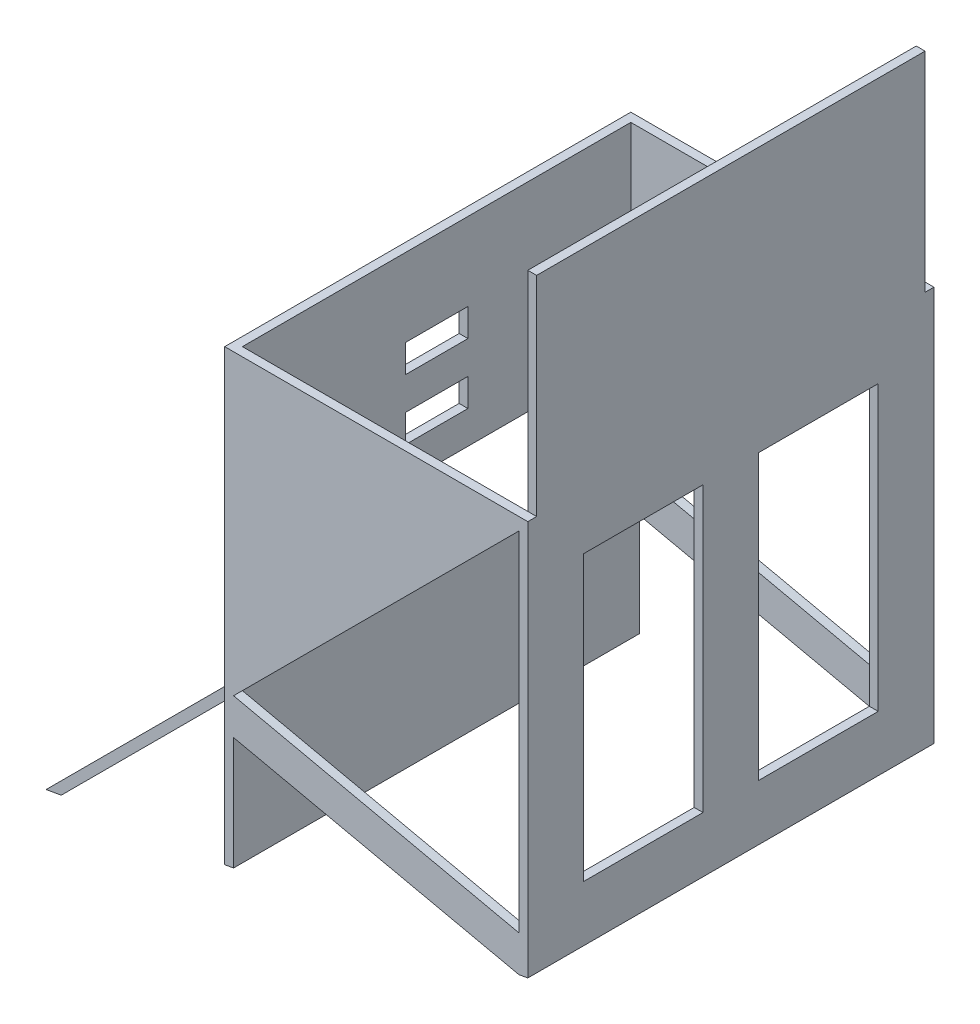
SolidWorks part; units mm, degrees
material "Teak"
ref_plane "Front Plane" through (0, 0, 0) normal (0, 0, 1) x (1, 0, 0)
ref_plane "Top Plane" through (0, 0, 0) normal (0, 1, 0) x (1, 0, 0)
ref_plane "Right Plane" through (0, 0, 0) normal (1, 0, 0) x (0, 0, -1)
sketch "Sketch1" plane through (0, 0, 0) normal (0, 1, 0) x (1, 0, 0)
  line L1 (-102.5, 139.5) -> (102.5, 139.5)
  line L2 (-102.5, 139.5) -> (-102.5, -139.5)
  line L3 (-102.5, -139.5) -> (102.5, -139.5)
  line L4 (102.5, 139.5) -> (102.5, -139.5)
  line L5 (-102.5, 139.5) -> (102.5, -139.5) construction
  line L6 (-102.5, -139.5) -> (102.5, 139.5) construction
  line L7 (-108.85, 145.85) -> (108.85, 145.85)
  line L8 (-108.85, 145.85) -> (-108.85, -145.85)
  line L9 (-108.85, -145.85) -> (108.85, -145.85)
  line L10 (108.85, 145.85) -> (108.85, -145.85)
  line L11 (-108.85, 145.85) -> (108.85, -145.85) construction
  line L12 (-108.85, -145.85) -> (108.85, 145.85) construction
  point P0 (0, 0)
  point P5 (0, 0)
  dimension "D1" = 279
  dimension "D2" = 205
  dimension "D3" = 6.35
  dimension "D4" = 6.35
sketch3d "3DSketch1"
  line L0 (102.5, 150, 0) -> (102.5, 0, 0) construction
  line L1 (102.5, 0, 0) -> (0, 0, 0) construction
  line L2 (102.5, 0, 102.7399) -> (102.5, 0, -102.7399) construction
  line L3 (102.5, 0, 0) -> (102.5, -285, 0) construction
  line L4 (102.5, -285, -65.8407) -> (102.5, -285, 65.8407) construction
  line L5 (102.5, 0, -139.5) -> (102.5, 0, 139.5) construction
  dimension "D1" = 150
  dimension "D2" = 285
ref_plane "Base Plane" through (51.25, -51.25, 0) normal (-0.7071, 0.7071, 0) x (0, 0, -1)
ref_plane "Launch Plane" through (51.8286, -293.9347, 0) normal (-0.1736, 0.9848, 0) x (0, 0, 1)
ref_plane "Box Bottom Plane (Approx)" through (0, -500, 0) normal (0, 1, 0) x (1, 0, 0)
extrude "Boss-Extrude1" add sketch "Sketch1" against normal up to surface (285 mm away) up to plane "Launch Plane"
sketch "Sketch7" plane through (0, 0, 0) normal (0, 0, 1) x (1, 0, 0)
  line L0 (102.5, 0) -> (-243.5111, -346.0111)
  line L1 (-243.5111, -346.0111) -> (-232.6084, -344.0887)
  line L2 (131.1629, 28.6629) -> (-28.6629, -131.1629) construction
  line L3 (119.735, 0) -> (-119.735, 0) construction
  line L4 (102.5, 0) -> (102.5, -8.9803)
  line L5 (102.5, -8.9803) -> (-232.6084, -344.0887)
  line L6 (123.1531, -281.3583) -> (-19.4958, -306.5112) construction
  dimension "D1" = 6.35
extrude "Boss-Extrude4" add sketch "Sketch7" against normal up to surface and the other way up to surface up to face at (0, -151.5368, -139.5) other way up to face at (0, -151.5368, 139.5)
sketch "Sketch8" plane through (0, 0, 0) normal (0, 1, 0) x (1, 0, 0)
  line L0 (108.85, 145.85) -> (108.85, -145.85) construction
  line L1 (102.5, 139.5) -> (108.85, 139.5)
  line L2 (102.5, 139.5) -> (102.5, -139.5)
  line L3 (102.5, -139.5) -> (108.85, -139.5)
  line L4 (108.85, 139.5) -> (108.85, -139.5)
  line L5 (-102.5, -139.5) -> (102.5, -139.5) construction
extrude "Boss-Extrude5" add sketch "Sketch8" along normal blind 150
sketch "Sketch4" plane through (0, 0, 0) normal (0, 0, 1) x (1, 0, 0)
  line L0 (-108.85, -211.35) -> (-102.5, -205)
  line L1 (-108.85, -143) -> (-102.5, -143)
  line L2 (-102.5, -205) -> (-102.5, 0) construction
  line L3 (-108.85, -211.35) -> (-108.85, -143)
  line L4 (-108.85, -322.2667) -> (-108.85, 0) construction
  line L5 (-102.5, -143) -> (-102.5, -205)
  line L7 (131.1629, 28.6629) -> (-28.6629, -131.1629) construction
  dimension "D2" = 62
extrude "Cut-Extrude1" cut sketch "Sketch4" against normal up to surface and the other way up to surface up to face at (-34.1667, -68.3333, -139.5) other way up to face at (-34.1667, -68.3333, 139.5)
sketch "Sketch6" plane through (0, 0, 0) normal (0, 0, 1) x (1, 0, 0)
  line L8 (-108.85, -99.5) -> (-102.5, -99.5)
  line L9 (-108.85, -99.5) -> (-108.85, -119.5)
  line L10 (-108.85, -119.5) -> (-102.5, -119.5)
  line L11 (-102.5, -99.5) -> (-102.5, -119.5)
  line L12 (-102.5, -143) -> (-102.5, -205) construction
  line L13 (-108.85, -56) -> (-102.5, -56)
  line L14 (-108.85, -56) -> (-108.85, -76)
  line L15 (-108.85, -76) -> (-102.5, -76)
  line L16 (-102.5, -56) -> (-102.5, -76)
  line L17 (-108.85, -143) -> (-102.5, -143) construction
  line L18 (-108.85, -211.35) -> (-108.85, -143) construction
  point P5 (-105.675, -99.5)
  dimension "D1" = 20
  dimension "D2" = 43.5
  dimension "D4" = 20
  dimension "D5" = 43.5
extrude "Cut-Extrude2" cut sketch "Sketch6" against normal mid plane 45
sketch "Sketch9" plane through (0, 0, 0) normal (0, 0, 1) x (1, 0, 0)
  line L0 (-102.5, -321.147) -> (-102.5, -239.9854)
  line L1 (108.85, -283.8803) -> (-108.85, -322.2667) construction
  line L2 (-102.5, -239.9854) -> (102.5, -285)
  line L3 (102.5, -285) -> (-102.5, -321.147)
  line L4 (-102.5, -213.9803) -> (102.5, -8.9803)
  line L5 (102.5, -8.9803) -> (102.5, -258.9949)
  line L6 (102.5, -258.9949) -> (-102.5, -213.9803)
  line L8 (-108.85, -322.2667) -> (-108.85, 0) construction
  line L10 (131.1629, 28.6629) -> (-28.6629, -131.1629) construction
  line L11 (108.85, -283.8803) -> (108.85, 0) construction
  dimension "D1" = 6.35
  dimension "D2" = 6.35
  dimension "D3" = 6.35
  dimension "D4" = 25.4
extrude "Cut-Extrude3" cut sketch "Sketch9" against normal through all both and the other way through all
sketch "Sketch10" plane through (108.85, 0, 0) normal (1, 0, 0) x (0, 0, -1)
  line L0 (145.85, -283.8803) -> (-145.85, -283.8803) construction
  line L3 (-20, -40) -> (-105.85, -40)
  line L6 (-20, -40) -> (20, -40) construction
  line L7 (0, 0) -> (0, -40) construction
  line L8 (-20, -40) -> (-20, -243.8803)
  line L9 (-20, -243.8803) -> (-105.85, -243.8803)
  line L10 (-105.85, -40) -> (-105.85, -243.8803)
  line L11 (20, -40) -> (105.85, -40)
  line L12 (20, -40) -> (20, -243.8803)
  line L13 (20, -243.8803) -> (105.85, -243.8803)
  line L14 (105.85, -40) -> (105.85, -243.8803)
  line L15 (-145.85, -283.8803) -> (-145.85, 0) construction
  dimension "D1" = 40
  dimension "D2" = 40
  dimension "D3" = 40
  dimension "D4" = 40
extrude "Cut-Extrude4" cut sketch "Sketch10" against normal up to next
equation "\"Frisbee Width\"=274"
equation "\"D1@Sketch1\"=\"Frisbee Width\"+5"
equation "\"Wall Thickness\"= 6.35"
equation "\"D3@Sketch1\"=\"Wall Thickness\""
equation "\"D4@Sketch1\"=\"Wall Thickness\""
equation "\"D2@Sketch4\"=85-23"
equation "\"D1@Sketch7\"=\"Wall Thickness\""
equation "\"D1@Sketch9\"=\"Wall Thickness\""
equation "\"D2@Sketch9\"=\"Wall Thickness\""
equation "\"D3@Sketch9\"=\"Wall Thickness\""
